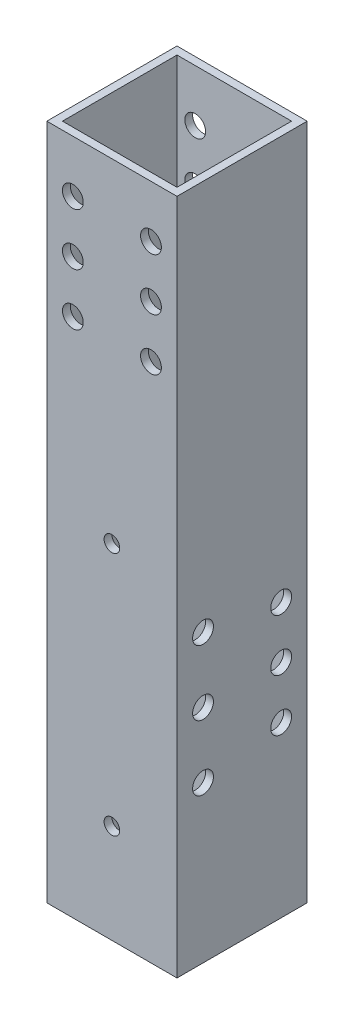
SolidWorks part; units mm, degrees
material "1060 Alloy"
ref_plane "Front Plane" through (0, 0, 0) normal (0, 0, 1) x (1, 0, 0)
ref_plane "Top Plane" through (0, 0, 0) normal (0, 1, 0) x (1, 0, 0)
ref_plane "Right Plane" through (0, 0, 0) normal (1, 0, 0) x (0, 0, -1)
sketch "Sketch3" plane through (0, 0, 0) normal (0, 1, 0) x (1, 0, 0)
  line L0 (0, 86.7063) -> (0, -87.1032) construction
  line L1 (-136.9048, 0) -> (130.9524, 0) construction
  line L7 (-12.5, 12.5) -> (12.5, 12.5)
  line L8 (-12.5, 12.5) -> (-12.5, -12.5)
  line L13 (-12.5, -12.5) -> (12.5, -12.5)
  line L14 (12.5, 12.5) -> (12.5, -12.5)
  line L15 (-12.5, 12.5) -> (12.5, -12.5) construction
  line L16 (-12.5, -12.5) -> (12.5, 12.5) construction
  line L17 (-11, 11) -> (11, 11)
  line L18 (-11, 11) -> (-11, -11)
  line L19 (-11, -11) -> (11, -11)
  line L20 (11, 11) -> (11, -11)
  line L21 (-11, 11) -> (11, -11) construction
  line L22 (-11, -11) -> (11, 11) construction
  point P5 (0, 0)
  point P10 (0, 0)
  dimension "D1" = 25
  dimension "D2" = 25
  dimension "D3" = 22
extrude "Boss-Extrude1" add sketch "Sketch3" along normal blind 65 and the other way blind 65
sketch "Sketch5" plane through (0, 0, -12.5) normal (0, 0, -1) x (-1, 0, 0)
  line L0 (-12.5, -65) -> (12.5, -65) construction
  circle A0 centre (0, -46) radius 1.5
  circle A1 centre (0, 1) radius 1.5
  dimension "D1" = 19
  dimension "D2" = 66
extrude "Cut-Extrude2" cut sketch "Sketch5" against normal blind 25
sketch "Sketch6" plane through (12.5, 0, 0) normal (1, 0, 0) x (0, 0, -1)
  line L0 (0, 0) -> (0, -102.9817) construction
  line L1 (-12.5, -65) -> (12.5, -65) construction
  circle A0 centre (7.5, -32.5) radius 2
  circle A1 centre (7.5, -12.5) radius 2
  circle A3 centre (-7.5, -35) radius 2
  circle A4 centre (-7.5, -10) radius 2
  circle A5 centre (7.5, -22.5) radius 2
  circle A6 centre (-7.5, -22.5) radius 2
  dimension "D2" = 10
  dimension "D9" = 12.5
  dimension "D3" = 7.5
  dimension "D4" = 7.5
  dimension "D5" = 7.5
  dimension "D6" = 7.5
  dimension "D7" = 32.5
  dimension "D8" = 10
  dimension "D10" = 30
  dimension "D11" = 12.5
extrude "Cut-Extrude3" cut sketch "Sketch6" against normal blind 25
sketch "Sketch7" plane through (0, 0, -12.5) normal (0, 0, -1) x (-1, 0, 0)
  line L0 (0, 0) -> (0, 70.1061) construction
  line L2 (-12.5, 65) -> (12.5, 65) construction
  circle A0 centre (7.5, 55) radius 2
  circle A1 centre (7.5, 45) radius 2
  circle A3 centre (-7.5, 55) radius 2
  circle A4 centre (-7.5, 45) radius 2
  circle A5 centre (-7.5, 35) radius 2
  circle A6 centre (7.5, 35) radius 2
  dimension "D1" = 7.5
  dimension "D5" = 10
  dimension "D2" = 7.5
  dimension "D3" = 7.5
  dimension "D4" = 7.5
  dimension "D6" = 10
  dimension "D7" = 10
  dimension "D8" = 10
  dimension "D9" = 7.5
  dimension "D10" = 10
  dimension "D11" = 7.5
  dimension "D12" = 10
extrude "Cut-Extrude4" cut sketch "Sketch7" against normal blind 25
